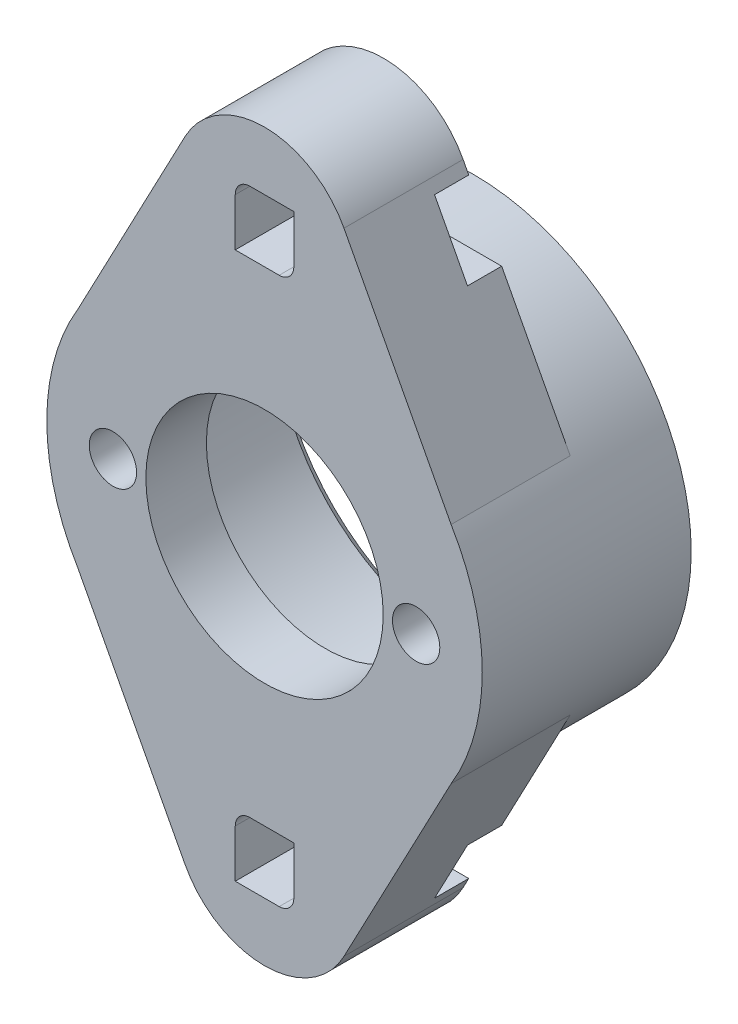
SolidWorks part; units mm, degrees
ref_plane "Front" through (0, 0, 0) normal (0, 0, 1) x (1, 0, 0)
ref_plane "Top" through (0, 0, 0) normal (0, 1, 0) x (1, 0, 0)
ref_plane "Right" through (0, 0, 0) normal (1, 0, 0) x (0, 0, -1)
sketch "Sketch1" plane through (0, 0, 0) normal (0, 0, 1) x (1, 0, 0)
  circle A2 centre (0, 0) radius 19.1 construction
  circle A3 centre (0, 0) radius 22.3
  circle A5 centre (0, 0) radius 12.155
  circle A6 centre (0, 0) radius 19.3
  circle A14 centre (-15.5275, 0) radius 1.6
  circle A17 centre (15.5275, 0) radius 1.6
  dimension "D5" = 0.2
  dimension "D6" = 3
extrude "Boss-Extrude1" add sketch "Sketch1" along normal blind 1 contours A6 A17 A14 A5 | A3 A6 region at (-21.6693, 0, 0) region at (-18.7541, 0, 0)
extrude "Boss-Extrude2" add sketch "Sketch1<3>" against normal blind 15.2 contours A3 A6 region at (-21.6693, 0, 0)
sketch "Sketch1<3>" plane through (0, 0, 0) normal (0, 0, 1) x (1, 0, 0) same geometry as "Sketch1"
sketch "Sketch3" plane through (0, 0, 1) normal (0, 0, 1) x (1, 0, 0)
  circle A0 centre (-15.5275, 0) radius 2.225 construction
  circle A1 centre (15.5275, 0) radius 2.225 construction
  circle A2 centre (-15.5275, 0) radius 2.425
  circle A3 centre (15.5275, 0) radius 2.425
  circle A4 centre (0, 0) radius 12.155 construction
  circle A5 centre (0, 0) radius 22.3
  circle A6 centre (0, 0) radius 22.3
  circle A7 centre (0, 0) radius 12.155
  dimension "D1" = 4.45
  dimension "D2" = 0.2
  dimension "D3" = 0
extrude "Boss-Extrude3" add sketch "Sketch3" along normal blind 2.5
sketch "Sketch4" plane through (0, 0, 3.5) normal (0, 0, 1) x (1, 0, 0)
  line L0 (0, 28) -> (0, -28) construction
  line L1 (-20.2747, -9.2859) -> (-8.1371, -32.2928)
  line L2 (20.2747, -9.2859) -> (8.1371, -32.2928)
  line L3 (0, 0) -> (10.274, 0) construction
  line L4 (-20.2747, -9.2859) -> (-8.1371, -32.2928)
  line L5 (20.2747, -9.2859) -> (8.1371, -32.2928)
  line L6 (-20.2747, -9.2859) -> (-8.1371, -32.2928)
  line L7 (20.2747, -9.2859) -> (8.1371, -32.2928)
  line L8 (-20.2747, -9.2859) -> (-8.1371, -32.2928)
  line L9 (20.2747, -9.2859) -> (8.1371, -32.2928)
  line L10 (20.2747, 9.2859) -> (8.1371, 32.2928)
  line L11 (-20.2747, 9.2859) -> (-8.1371, 32.2928)
  line L12 (20.2747, 9.2859) -> (8.1371, 32.2928)
  line L13 (-20.2747, 9.2859) -> (-8.1371, 32.2928)
  line L14 (20.2747, 9.2859) -> (8.1371, 32.2928)
  line L15 (-20.2747, 9.2859) -> (-8.1371, 32.2928)
  line L16 (20.2747, 9.2859) -> (8.1371, 32.2928)
  line L17 (-20.2747, 9.2859) -> (-8.1371, 32.2928)
  line L18 (-2.8, -28) -> (2.8, -28)
  line L19 (3, -24.8) -> (-3, -24.8)
  line L20 (2.8, -31) -> (-2.8, -31) construction
  line L21 (2.8, -31) -> (2.8, -25) construction
  line L22 (2.8, -25) -> (-2.8, -25) construction
  line L23 (-2.8, -31) -> (-2.8, -25) construction
  line L24 (2.8, -31) -> (-2.8, -25) construction
  line L25 (2.8, -25) -> (-2.8, -31) construction
  line L26 (-3, -31.2) -> (-3, -24.8)
  line L27 (3, -31.2) -> (-3, -31.2)
  line L28 (3, -31.2) -> (3, -24.8)
  line L29 (3, 31.2) -> (-3, 31.2)
  line L30 (3, 31.2) -> (3, 24.8)
  line L31 (3, 24.8) -> (-3, 24.8)
  line L32 (-3, 31.2) -> (-3, 24.8)
  arc A2 (-8.1371, -32.2928) -> (8.1371, -32.2928) centre (0, -28) ccw
  arc A3 (8.1371, -32.2928) -> (-8.1371, -32.2928) centre (0, -28) ccw construction
  circle A4 centre (0, 0) radius 22.3 construction
  circle A5 centre (0, 0) radius 22.3
  arc A7 (8.1371, -32.2928) -> (-8.1371, -32.2928) centre (0, -28) ccw construction
  arc A8 (8.1371, 32.2928) -> (-8.1371, 32.2928) centre (0, 28) cw construction
  arc A9 (8.1371, 32.2928) -> (-8.1371, 32.2928) centre (0, 28) cw construction
  arc A11 (-8.1371, 32.2928) -> (8.1371, 32.2928) centre (0, 28) cw
  point P28 (0, -28)
  circle M2 centre (0, 0) radius 22.3
  dimension "D1" = 6
  dimension "D4" = 28
  dimension "D5" = 5.6
  dimension "D2" = 0.2
extrude "Boss-Extrude4" add sketch "Sketch4" against normal blind 6 contours A11 L11 L10 M2 | L1 A2 L2 M2 region at (0, -22.7606, 3.5) region at (-13.2164, 21.6777, 3.5)
chamfer "Chamfer1" distance 1 angle 45 1 edges at (19.3, 0, -15.2)
sketch "Sketch5" plane through (0, 0, -2.5) normal (0, 0, -1) x (-1, 0, 0)
  line L0 (0, 0) -> (-39.5514, 0) construction
  line L5 (-16.4788, -31.2) -> (16.4788, -31.2)
  line L6 (-16.4788, -31.2) -> (-16.4788, -24.8)
  line L7 (-16.4788, -24.8) -> (16.4788, -24.8)
  line L8 (16.4788, -31.2) -> (16.4788, -24.8)
  line L9 (-3, -24.8) -> (3, -24.8) construction
  line L10 (-3, -31.2) -> (3, -31.2) construction
  line L11 (-16.4788, 24.8) -> (16.4788, 31.2) construction
  line L12 (8.1371, -32.2928) -> (19.1106, -11.4924)
  line L13 (-19.1106, -11.4924) -> (-8.1371, -32.2928)
  line L14 (8.1371, -32.2928) -> (19.1106, -11.4924)
  line L15 (-19.1106, -11.4924) -> (-8.1371, -32.2928)
  line L16 (-8.1371, 32.2928) -> (-19.1106, 11.4924)
  line L17 (19.1106, 11.4924) -> (8.1371, 32.2928)
  line L18 (-8.1371, 32.2928) -> (-19.1106, 11.4924)
  line L19 (19.1106, 11.4924) -> (8.1371, 32.2928)
  line L20 (-16.4788, 31.2) -> (16.4788, 24.8) construction
  line L21 (-19.1106, 11.4924) -> (-8.1371, 32.2928)
  line L22 (8.1371, 32.2928) -> (19.1106, 11.4924)
  line L23 (16.4788, 31.2) -> (16.4788, 24.8)
  line L24 (-16.4788, 24.8) -> (16.4788, 24.8)
  line L25 (-16.4788, 31.2) -> (-16.4788, 24.8)
  line L26 (-16.4788, 31.2) -> (16.4788, 31.2)
  arc A6 (-19.1106, -11.4924) -> (19.1106, -11.4924) centre (0, 0) ccw
  arc A7 (-8.1371, -32.2928) -> (8.1371, -32.2928) centre (0, -28) ccw
  arc A8 (-19.1106, -11.4924) -> (19.1106, -11.4924) centre (0, 0) ccw
  arc A9 (-8.1371, -32.2928) -> (8.1371, -32.2928) centre (0, -28) ccw
  arc A10 (8.1371, 32.2928) -> (-8.1371, 32.2928) centre (0, 28) ccw
  arc A11 (19.1106, 11.4924) -> (-19.1106, 11.4924) centre (0, 0) ccw
  arc A12 (8.1371, 32.2928) -> (-8.1371, 32.2928) centre (0, 28) ccw
  arc A13 (19.1106, 11.4924) -> (-19.1106, 11.4924) centre (0, 0) ccw
  arc A14 (-8.1371, 32.2928) -> (8.1371, 32.2928) centre (0, 28) cw
  arc M1 (8.1371, 32.2928) -> (-8.1371, 32.2928) centre (0, 28) ccw
  line M2 (-8.1371, 32.2928) -> (-19.1106, 11.4924)
  arc M3 (-19.1106, 11.4924) -> (19.1106, 11.4924) centre (0, 0) cw
  line M4 (19.1106, 11.4924) -> (8.1371, 32.2928)
  dimension "D1" = 0
  dimension "D2" = 0
extrude "Boss-Extrude5" add sketch "Sketch5" along normal blind 3.5 contours L24 L21 M3 M4 | L26 M2 M4 M1 | A8 L15 L7 L14 | L15 A9 L14 L5 region at (0, -33.6811, -2.5) region at (15.2423, -17.9573, -2.5) region at (0, 33.6811, -2.5) region at (0, 24.3953, -2.5)
fillet "Fillet1" radius 1.5 4 edges at (3, -31.2, 0.5) (-3, -24.8, 0.5) (3, 24.8, 0.5) (-3, 31.2, 0.5)
sketch "Sketch6" plane through (0, 0, 3.5) normal (0, 0, 1) x (1, 0, 0)
  line L4 (-3, 29.7) -> (-3, 24.8)
  line L5 (3, 31.2) -> (-1.5, 31.2)
  line L6 (3, 26.3) -> (3, 31.2)
  line L7 (-3, 24.8) -> (1.5, 24.8)
  line L12 (-3, 29.7) -> (-3, 24.8)
  line L13 (3, 31.2) -> (-1.5, 31.2)
  line L14 (3, 26.3) -> (3, 31.2)
  line L15 (-3, 24.8) -> (1.5, 24.8)
  line L16 (3, -29.7) -> (3, -24.8)
  line L17 (-3, -31.2) -> (1.5, -31.2)
  line L18 (-3, -26.3) -> (-3, -31.2)
  line L19 (3, -24.8) -> (-1.5, -24.8)
  line L20 (3, -29.7) -> (3, -24.8)
  line L21 (-3, -31.2) -> (1.5, -31.2)
  line L22 (-3, -26.3) -> (-3, -31.2)
  line L23 (3, -24.8) -> (-1.5, -24.8)
  line L24 (-19.1106, -11.4924) -> (-8.1371, -32.2928)
  line L25 (8.1371, -32.2928) -> (19.1106, -11.4924)
  line L26 (19.1106, 11.4924) -> (8.1371, 32.2928)
  line L27 (-8.1371, 32.2928) -> (-19.1106, 11.4924)
  line L28 (-19.1106, -11.4924) -> (-8.1371, -32.2928)
  line L29 (8.1371, -32.2928) -> (19.1106, -11.4924)
  line L30 (19.1106, 11.4924) -> (8.1371, 32.2928)
  line L31 (-8.1371, 32.2928) -> (-19.1106, 11.4924)
  circle A1 centre (0, 0) radius 12.155
  arc A2 (-1.5, 31.2) -> (-3, 29.7) centre (-1.5, 29.7) ccw
  arc A3 (1.5, 24.8) -> (3, 26.3) centre (1.5, 26.3) ccw
  arc A4 (-1.5, 31.2) -> (-3, 29.7) centre (-1.5, 29.7) ccw
  arc A5 (1.5, 24.8) -> (3, 26.3) centre (1.5, 26.3) ccw
  arc A6 (1.5, -31.2) -> (3, -29.7) centre (1.5, -29.7) ccw
  arc A7 (-1.5, -24.8) -> (-3, -26.3) centre (-1.5, -26.3) ccw
  arc A12 (1.5, -31.2) -> (3, -29.7) centre (1.5, -29.7) ccw
  arc A13 (-1.5, -24.8) -> (-3, -26.3) centre (-1.5, -26.3) ccw
  circle A14 centre (0, 0) radius 12.155
  circle A15 centre (-15.5275, 0) radius 2.425
  circle A16 centre (-15.5275, 0) radius 2.425
  circle A17 centre (15.5275, 0) radius 2.425
  circle A18 centre (15.5275, 0) radius 2.425
  arc A22 (-19.1106, 11.4924) -> (-19.1106, -11.4924) centre (0, 0) ccw
  arc A23 (-8.1371, -32.2928) -> (8.1371, -32.2928) centre (0, -28) ccw
  arc A24 (19.1106, -11.4924) -> (19.1106, 11.4924) centre (0, 0) ccw
  arc A25 (8.1371, 32.2928) -> (-8.1371, 32.2928) centre (0, 28) ccw
  arc A26 (-19.1106, 11.4924) -> (-19.1106, -11.4924) centre (0, 0) ccw
  arc A27 (-8.1371, -32.2928) -> (8.1371, -32.2928) centre (0, -28) ccw
  arc A28 (19.1106, -11.4924) -> (19.1106, 11.4924) centre (0, 0) ccw
  arc A29 (8.1371, 32.2928) -> (-8.1371, 32.2928) centre (0, 28) ccw
  dimension "D1" = 0
  dimension "D2" = 0
  dimension "D3" = 0
  dimension "D4" = 0
  dimension "D5" = 0
  dimension "D6" = 0
extrude "Boss-Extrude6" add sketch "Sketch6" along normal offset from surface (2.7 mm away) 0.2 offset beyond the face yes
